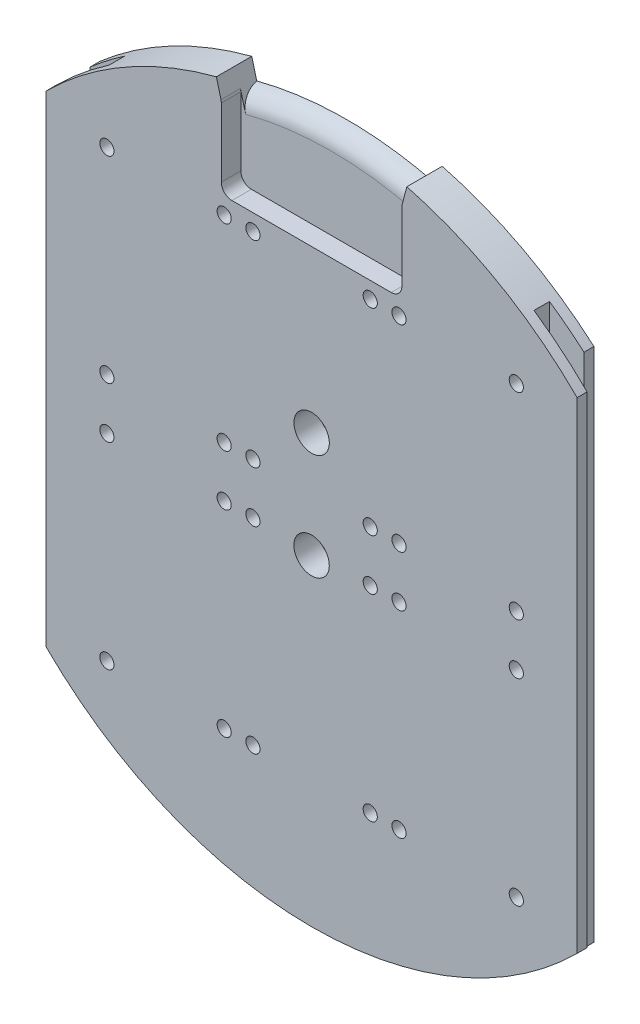
SolidWorks part; units mm, degrees
material "ABS"
ref_plane "Plano frontal" through (0, 0, 0) normal (0, 0, 1) x (1, 0, 0)
ref_plane "Plano superior" through (0, 0, 0) normal (0, 1, 0) x (1, 0, 0)
ref_plane "Plano direito" through (0, 0, 0) normal (1, 0, 0) x (0, 0, -1)
sketch "Esboço1" plane through (0, 0, 0) normal (0, 0, 1) x (1, 0, 0)
  line L0 (0, 0) -> (0, -108.75)
  line L1 (120, -108.75) -> (120, 0)
  line L2 (60, -11.4098) -> (60, -97.3402) construction
  line L3 (120, -54.375) -> (-37.4329, -54.375) construction
  line L8 (12.1875, -86.25) -> (107.8125, -22.5) construction
  line L9 (12.1875, -22.5) -> (107.8125, -86.25) construction
  arc A4 (0, 0) -> (120, 0) centre (60, -60.208) cw
  arc A5 (0, -108.75) -> (120, -108.75) centre (60, -48.542) ccw
  point P9 (60, -54.375)
  point P17 (60, 24.792)
  dimension "D1" = 108.75
  dimension "D5" = 85
  dimension "D2" = 63.75
  dimension "D3" = 95.625
extrude "Ressalto-extrusão1" add sketch "Esboço1" along normal blind 8
sketch "Esboço5" plane through (0, 0, 8) normal (0, 0, 1) x (1, 0, 0)
  line L0 (60, 24.792) -> (60, -133.542) construction
  line L1 (44.6956, -48.875) -> (75, -48.875) construction
  line L5 (44.6956, -79.875) -> (75, -79.875)
  line L6 (44.6956, -79.875) -> (44.6956, -17.875)
  line L7 (44.6956, -17.875) -> (75, -17.875)
  line L8 (75, -79.875) -> (75, -17.875)
  arc A0 (120, 0) -> (0, 0) centre (60, -60.208) ccw construction
  arc A1 (0, -108.75) -> (120, -108.75) centre (60, -48.542) ccw construction
  circle A2 centre (60, -60.875) radius 4
  circle A4 centre (60, -36.875) radius 4
  dimension "D1" = 8
  dimension "D2" = 12
  dimension "D4" = 30.3044
  dimension "D3" = 62
  dimension "D5" = 15
  dimension "D6" = 73.667
extrude "Corte-extrusão3" cut sketch "Esboço5" against normal blind 5.6 contours A4 | A2
sketch "Esboço7" plane through (0, 0, 0) normal (0, 0, -1) x (-1, 0, 0)
  line L0 (-60, 24.792) -> (-60, -133.542) construction
  line L1 (-120, -54.375) -> (0, -54.375) construction
  line L2 (-120, -108.75) -> (-120, 0) construction
  line L3 (0, 0) -> (0, -108.75) construction
  line L4 (-106.25, -26.375) -> (-73.25, -26.375) construction
  line L5 (-13.75, -26.375) -> (-46.75, -26.375) construction
  line L6 (-13.75, -82.375) -> (-46.75, -82.375) construction
  line L7 (-106.25, -82.375) -> (-73.25, -82.375) construction
  arc A0 (0, 0) -> (-120, 0) centre (-60, -60.208) ccw construction
  arc A1 (-120, -108.75) -> (0, -108.75) centre (-60, -48.542) ccw construction
  circle A2 centre (-73.25, -48.625) radius 1.6
  circle A3 centre (-79.75, -48.625) radius 1.6
  circle A4 centre (-106.25, -48.625) radius 1.6
  circle A5 centre (-73.25, -4.125) radius 1.6
  circle A6 centre (-106.25, -4.125) radius 1.6
  circle A7 centre (-79.75, -4.125) radius 1.6
  circle A8 centre (-40.25, -4.125) radius 1.6
  circle A9 centre (-13.75, -4.125) radius 1.6
  circle A10 centre (-46.75, -4.125) radius 1.6
  circle A11 centre (-13.75, -48.625) radius 1.6
  circle A12 centre (-40.25, -48.625) radius 1.6
  circle A13 centre (-46.75, -48.625) radius 1.6
  circle A14 centre (-46.75, -60.125) radius 1.6
  circle A15 centre (-40.25, -60.125) radius 1.6
  circle A16 centre (-13.75, -60.125) radius 1.6
  circle A17 centre (-46.75, -104.625) radius 1.6
  circle A18 centre (-13.75, -104.625) radius 1.6
  circle A19 centre (-40.25, -104.625) radius 1.6
  circle A20 centre (-79.75, -104.625) radius 1.6
  circle A21 centre (-106.25, -104.625) radius 1.6
  circle A22 centre (-73.25, -104.625) radius 1.6
  circle A23 centre (-106.25, -60.125) radius 1.6
  circle A24 centre (-79.75, -60.125) radius 1.6
  circle A25 centre (-73.25, -60.125) radius 1.6
  dimension "D1" = 3.2
  dimension "D2" = 3.2
  dimension "D3" = 3.2
  dimension "D4" = 5.75
  dimension "D5" = 13.25
  dimension "D6" = 6.5
  dimension "D7" = 26.5
  dimension "D8" = 22.25
extrude "Corte-extrusão4" cut sketch "Esboço7" against normal through all
sketch "Esboço9" plane through (0, 0, 8) normal (0, 0, 1) x (1, 0, 0)
  line L0 (39.6, 17.7677) -> (38.4864, 22.0244)
  line L1 (60, 24.792) -> (60, -133.542) construction
  line L2 (80.4, 17.7677) -> (81.5136, 22.0244)
  arc A0 (120, 0) -> (0, 0) centre (60, -60.208) ccw construction
  arc A1 (81.5136, 22.0244) -> (38.4864, 22.0244) centre (60, -60.208) ccw
  arc A2 (80.4, 17.7677) -> (39.6, 17.7677) centre (60, -60.208) ccw
  arc A3 (81.5136, 22.0244) -> (0, 0) centre (60, -60.208) ccw construction
  arc A4 (80.4, 17.7677) -> (3.1059, -3.1166) centre (60, -60.208) ccw construction
  arc A5 (0, -108.75) -> (120, -108.75) centre (60, -48.542) ccw construction
  dimension "D2" = 20.4
  dimension "D1" = 4.4
extrude "Corte-extrusão6" cut sketch "Esboço9" against normal through all
sketch "Esboço10" plane through (0, 0, 8) normal (0, 0, 1) x (1, 0, 0)
  line L0 (39.6, 17.7677) -> (39.6, -0.4323)
  line L1 (39.6, -0.4323) -> (80.4, -0.4323)
  line L2 (80.4, -0.4323) -> (80.4, 17.7677)
  arc A0 (80.4, 17.7677) -> (39.6, 17.7677) centre (60, -60.208) ccw construction
  arc A1 (80.4, 17.7677) -> (39.6, 17.7677) centre (60, -60.208) ccw
  dimension "D1" = 18.2
extrude "Corte-extrusão7" cut sketch "Esboço10" against normal blind 4.4 contours L2 A1 L0 L1
fillet "Filete1" radius 2.4 4 edges at (80.4, -0.4323, 5.8) (39.6, -0.4323, 5.8) (80.4, 17.7677, 5.8) (39.6, 17.7677, 5.8)
fillet "Filete2" radius 4.4 1 edges at (60, 20.392, 3.6)
sketch "Esboço11" plane through (0, 0, 0) normal (-1, 0, 0) x (0, 0, 1)
  line L1 (2.25, -128.75) -> (5.75, -128.75)
  line L2 (2.25, -128.75) -> (2.25, 21.25)
  line L3 (2.25, 21.25) -> (5.75, 21.25)
  line L4 (5.75, -128.75) -> (5.75, 21.25)
  line L5 (0, 0) -> (0, -108.75) construction
  line L6 (8, -108.75) -> (0, -108.75) construction
  dimension "D1" = 3.5
  dimension "D2" = 150
  dimension "D3" = 2.25
  dimension "D4" = 20
extrude "Corte-extrusão8" cut sketch "Esboço11" against normal blind 12
sketch "Esboço12" plane through (120, 0, 0) normal (1, 0, 0) x (0, 0, -1)
  line L1 (-2.25, -128.75) -> (-5.75, -128.75)
  line L2 (-2.25, -128.75) -> (-2.25, 21.25)
  line L3 (-2.25, 21.25) -> (-5.75, 21.25)
  line L4 (-5.75, -128.75) -> (-5.75, 21.25)
  line L5 (-8, -108.75) -> (-8, 0) construction
  line L6 (-8, -108.75) -> (0, -108.75) construction
  dimension "D1" = 3.5
  dimension "D2" = 150
  dimension "D3" = 2.25
  dimension "D4" = 20
extrude "Corte-extrusão9" cut sketch "Esboço12" against normal blind 12
sketch "Esboço13" plane through (0, 0, 0) normal (0, 0, -1) x (-1, 0, 0)
  line L0 (-60, 20.392) -> (-60, -133.542) construction
  line L1 (0, -54.375) -> (-120.2, -54.375) construction
  line L2 (-120.2, 22.6494) -> (-115.8, 22.6494)
  line L3 (-120.2, 22.6494) -> (-120.2, -134.167)
  line L4 (-120.2, -134.167) -> (-115.8, -134.167)
  line L5 (-115.8, 22.6494) -> (-115.8, -134.167)
  line L6 (0, 0) -> (0, -108.75) construction
  line L7 (-4.2, 22.6494) -> (-4.2, -134.167)
  line L8 (0.2, -134.167) -> (-4.2, -134.167)
  line L9 (0.2, 22.6494) -> (0.2, -134.167)
  line L10 (0.2, 22.6494) -> (-4.2, 22.6494)
  arc A0 (-39.6, 17.7677) -> (-80.4, 17.7677) centre (-60, -60.208) ccw construction
  arc A1 (-120, -108.75) -> (0, -108.75) centre (-60, -48.542) ccw construction
  dimension "D1" = 4.4
  dimension "D2" = 156.8164
  dimension "D3" = 55.8
  dimension "D4" = 79.792
extrude "Corte-extrusão10" cut sketch "Esboço13" against normal blind 5.75
